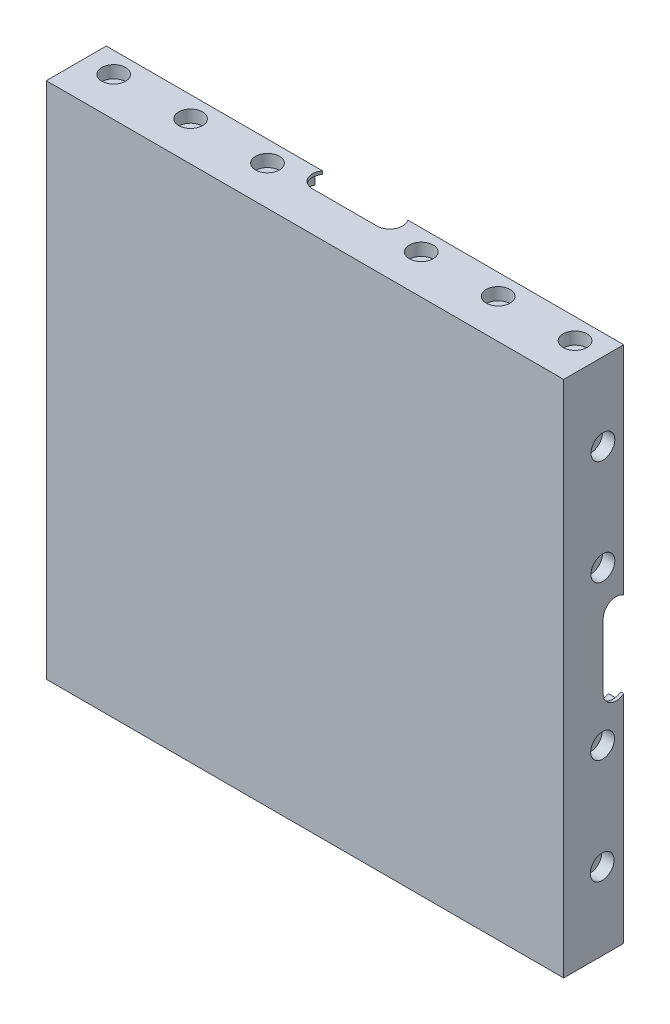
SolidWorks part; units mm, degrees
note: The reader was unsure of these and kept them because the rebuilt part matched: shared geometry of "Sketch1<3>", "Sketch1<4>", "Sketch9<3>", "Sketch9<4>", "Sketch13<2>", "Sketch14<2>".
ref_plane "Front Plane" through (0, 0, 0) normal (0, 0, 1) x (1, 0, 0)
ref_plane "Top Plane" through (0, 0, 0) normal (0, 1, 0) x (1, 0, 0)
ref_plane "Right Plane" through (0, 0, 0) normal (1, 0, 0) x (0, 0, -1)
sketch "Sketch1" plane through (0, 0, 0) normal (0, 0, 1) x (1, 0, 0)
  line L6 (-63, 3.7) -> (-61.15, 3.7) construction
  line L7 (-63, -63) -> (63, -63)
  line L8 (-63, -63) -> (-63, 63)
  line L9 (-63, 63) -> (63, 63)
  line L10 (63, -63) -> (63, 63)
  line L11 (-61, 61) -> (61, 61)
  line L12 (-61, 61) -> (-61, -61)
  line L13 (-61, -61) -> (61, -61)
  line L14 (61, 61) -> (61, -61)
  line L15 (-63, 7.7) -> (-61, 7.7)
  line L16 (-63, 7.7) -> (-63, -7.7)
  line L17 (-63, -7.7) -> (-61, -7.7)
  line L18 (-61, 7.7) -> (-61, -7.7)
  line L19 (-61.15, -3.7) -> (-63, -3.7) construction
  line L20 (-3.7, 61.45) -> (-3.7, 63) construction
  line L21 (-7.7, 61) -> (7.7, 61)
  line L22 (-7.7, 61) -> (-7.7, 63)
  line L23 (-7.7, 63) -> (7.7, 63)
  line L24 (7.7, 61) -> (7.7, 63)
  line L26 (3.7, 63) -> (3.7, 61.45) construction
  line L27 (-61, 0) -> (61, 0) construction
  line L28 (0, 61) -> (0, -61) construction
  line L29 (63, -7.7) -> (61, -7.7)
  line L30 (61, 7.7) -> (61, -7.7)
  line L31 (63, 7.7) -> (61, 7.7)
  line L32 (63, 7.7) -> (63, -7.7)
  line L33 (-7.7, -63) -> (7.7, -63)
  line L34 (7.7, -61) -> (7.7, -63)
  line L35 (-7.7, -61) -> (7.7, -61)
  line L36 (-7.7, -61) -> (-7.7, -63)
  dimension "D1" = 4
  dimension "D2" = 4
  dimension "D3" = 4
  dimension "D4" = 4
  dimension "D5" = 2
  dimension "D6" = 2
  dimension "D7" = 2
  dimension "D8" = 2
extrude "Boss-Extrude1" add sketch "Sketch1" along normal blind 3 from offset 0.4 contours L11 L22 L9 L8 L15 L12 | L36 L13 L12 L17 L8 L7 | L13 L34 L7 L10 L29 L14 | L31 L10 L9 L24 L11 L14
extrude "Boss-Extrude2" add sketch "Sketch1<3>" along normal up to surface (2.85 mm away) from surface at 3.4 contours L8 L17 L12 L15 | L11 L22 L9 L8 L15 L12 | L36 L13 L12 L17 L8 L7 | L13 L34 L7 L10 L29 L14 | L31 L10 L9 L24 L11 L14 | L10 L31 L14 L29 | L13 L36 L7 L34 | L11 L24 L9 L22 starting at face at (43.9, 43.9, 3.4)
sketch "Sketch1<3>" plane through (0, 0, 0) normal (0, 0, 1) x (1, 0, 0) same geometry as "Sketch1"
extrude "Boss-Extrude3" add sketch "Sketch1<4>" against normal up to surface (7.7671 mm away) from surface contours L14 L11 L12 L13 | L8 L17 L12 L15 | L11 L22 L9 L8 L15 L12 | L36 L13 L12 L17 L8 L7 | L13 L36 L7 L34 | L13 L34 L7 L10 L29 L14 | L10 L31 L14 L29 | L31 L10 L9 L24 L11 L14 | L11 L24 L9 L22
sketch "Sketch1<4>" plane through (0, 0, 0) normal (0, 0, 1) x (1, 0, 0) same geometry as "Sketch1"
sketch "Sketch2" plane through (0, 63, 0) normal (0, 1, 0) x (1, 0, 0)
  line L0 (-8.5, -0.4) -> (8.5, -0.4) construction
  line L1 (-8.5, 4.6) -> (8.5, 4.6)
  line L2 (-8.5, -5.4) -> (8.5, -5.4)
  line L3 (-8.5, 3.6) -> (8.5, 3.6) construction
  line L4 (8.5, -4.4) -> (-8.5, -4.4) construction
  line L6 (-63, 1.6) -> (63, 1.6)
  line L7 (-63, 1.6) -> (-63, -14.0171)
  line L8 (-63, -14.0171) -> (63, -14.0171)
  line L9 (63, 1.6) -> (63, -14.0171)
  arc A0 (-8.5, 4.6) -> (-8.5, -5.4) centre (-8.5, -0.4) ccw
  arc A1 (8.5, -5.4) -> (8.5, 4.6) centre (8.5, -0.4) ccw
  arc A2 (-8.5, 3.6) -> (-8.5, -4.4) centre (-8.5, -0.4) ccw construction
  point P2 (0, -0.4)
  point P7 (0, 0)
  point P8 (0, 0)
  point P9 (62.1074, -13.2373)
  point P20 (-12.5, -0.4)
  point P21 (-13.5, -0.4)
  point P23 (13.5, -0.4)
  dimension "D1" = 1
  dimension "D2" = 1
  dimension "D3" = 1
  dimension "D4" = 1
extrude "Boss-Extrude4" add sketch "Sketch2" along normal offset from surface (3.85 mm away) 0.2
sketch "Sketch3" plane through (63, 0, 0) normal (1, 0, 0) x (0, 0, -1)
  line L0 (-0.4, 8.5) -> (-0.4, -8.5) construction
  line L1 (4.6, 8.5) -> (4.6, -8.5)
  line L2 (-5.4, 8.5) -> (-5.4, -8.5)
  line L3 (3.6, 8.5) -> (3.6, -8.5) construction
  line L4 (-4.4, -8.5) -> (-4.4, 8.5) construction
  line L6 (1.6, 66.85) -> (-14.0171, 66.85)
  line L7 (1.6, 66.85) -> (1.6, -63)
  line L8 (1.6, -63) -> (-14.0171, -63)
  line L9 (-14.0171, 66.85) -> (-14.0171, -63)
  arc A0 (4.6, 8.5) -> (-5.4, 8.5) centre (-0.4, 8.5) ccw
  arc A1 (-5.4, -8.5) -> (4.6, -8.5) centre (-0.4, -8.5) ccw
  arc A2 (3.6, 8.5) -> (-4.4, 8.5) centre (-0.4, 8.5) ccw construction
  point P2 (-0.4, 0)
  point P12 (-0.4, -13.5)
  point P16 (-0.4, 12.5)
  point P17 (-0.4, 13.5)
  point P22 (0, 0)
  point P23 (0, 0)
  point P24 (0, 0)
  point P25 (-12.5051, -61.7984)
  dimension "D1" = 1
  dimension "D2" = 1
  dimension "D3" = 1
  dimension "D4" = 1
extrude "Boss-Extrude6" add sketch "Sketch3" along normal offset from surface (3.45 mm away) 0.2
sketch "Sketch4" plane through (0, -63, 0) normal (0, -1, 0) x (1, 0, 0)
  line L0 (8.5, 0.4) -> (-8.5, 0.4) construction
  line L1 (8.5, -4.6) -> (-8.5, -4.6)
  line L2 (8.5, 5.4) -> (-8.5, 5.4)
  line L3 (8.5, -3.6) -> (-8.5, -3.6) construction
  line L4 (-8.5, 4.4) -> (8.5, 4.4) construction
  line L6 (66.45, -1.6) -> (-63, -1.6)
  line L7 (66.45, -1.6) -> (66.45, 14.0171)
  line L8 (66.45, 14.0171) -> (-63, 14.0171)
  line L9 (-63, -1.6) -> (-63, 14.0171)
  arc A0 (8.5, -4.6) -> (8.5, 5.4) centre (8.5, 0.4) ccw
  arc A1 (-8.5, 5.4) -> (-8.5, -4.6) centre (-8.5, 0.4) ccw
  arc A2 (8.5, -3.6) -> (8.5, 4.4) centre (8.5, 0.4) ccw construction
  point P2 (0, 0.4)
  point P7 (0, 0)
  point P13 (-13.5, 0.4)
  point P14 (13.5, 0.4)
  point P18 (12.5, 0.4)
  point P23 (0, 0)
  point P26 (-61.9955, 13.332)
  dimension "D1" = 1
  dimension "D2" = 1
  dimension "D3" = 1
  dimension "D4" = 1
extrude "Boss-Extrude9" add sketch "Sketch4" along normal offset from surface (3.55 mm away) 0.2
sketch "Sketch5" plane through (-63, 0, 0) normal (-1, 0, 0) x (0, 0, 1)
  line L0 (0.4, -8.5) -> (0.4, 8.5) construction
  line L1 (-4.6, -8.5) -> (-4.6, 8.5)
  line L2 (5.4, -8.5) -> (5.4, 8.5)
  line L3 (-3.6, -8.5) -> (-3.6, 8.5) construction
  line L5 (4.4, 8.5) -> (4.4, -8.5) construction
  line L7 (-1.6, -66.55) -> (14.0171, -66.55)
  line L8 (-1.6, -66.55) -> (-1.6, 66.85)
  line L9 (-1.6, 66.85) -> (14.0171, 66.85)
  line L10 (14.0171, -66.55) -> (14.0171, 66.85)
  arc A0 (-4.6, -8.5) -> (5.4, -8.5) centre (0.4, -8.5) ccw
  arc A1 (5.4, 8.5) -> (-4.6, 8.5) centre (0.4, 8.5) ccw
  arc A3 (-3.6, -8.5) -> (4.4, -8.5) centre (0.4, -8.5) ccw construction
  point P2 (0.4, 0)
  point P12 (0.4, 13.5)
  point P14 (0.4, -12.5)
  point P15 (0.4, -13.5)
  point P24 (0, 0)
  point P25 (0, 0)
  point P26 (13.1514, 63.8467)
  point P29 (0, 0)
  dimension "D3" = 1
  dimension "D1" = 1
  dimension "D2" = 1
  dimension "D4" = 1
extrude "Boss-Extrude10" add sketch "Sketch5" along normal offset from surface (3.55 mm away) 0.2
sketch "Sketch6" plane through (-66.55, 0, 0) normal (-1, 0, 0) x (0, 0, 1)
  line L0 (0.4, -8.4) -> (0.4, 8.4) construction
  line L1 (-2.95, -8.4) -> (-2.95, 8.4)
  line L2 (3.75, -8.4) -> (3.75, 8.4)
  line L3 (-2.45, -8.4) -> (-2.45, 8.4) construction
  line L4 (3.25, 8.4) -> (3.25, -8.4) construction
  line L6 (-1.6, -66.55) -> (14.0171, -66.55)
  line L7 (-1.6, -66.55) -> (-1.6, 66.85)
  line L8 (-1.6, 66.85) -> (14.0171, 66.85)
  line L9 (14.0171, -66.55) -> (14.0171, 66.85)
  arc A0 (-2.95, -8.4) -> (3.75, -8.4) centre (0.4, -8.4) ccw
  arc A1 (3.75, 8.4) -> (-2.95, 8.4) centre (0.4, 8.4) ccw
  arc A2 (3.25, 8.4) -> (-2.45, 8.4) centre (0.4, 8.4) ccw construction
  point P2 (0.4, 0)
  point P14 (0.4, 11.25)
  point P15 (0.4, 11.75)
  point P17 (0.4, -11.75)
  point P24 (0, 0)
  point P26 (13.7412, 65.7953)
  dimension "D1" = 0.5
  dimension "D2" = 0.5
  dimension "D3" = 0.5
  dimension "D4" = 0.5
extrude "Boss-Extrude11" add sketch "Sketch6" along normal up to surface (0.8 mm away)
sketch "Sketch7" plane through (0, -66.55, 0) normal (0, -1, 0) x (1, 0, 0)
  line L0 (8.4, 0.4) -> (-8.4, 0.4) construction
  line L6 (8.4, -2.95) -> (-8.4, -2.95)
  line L7 (8.4, 3.75) -> (-8.4, 3.75)
  line L8 (8.4, -2.45) -> (-8.4, -2.45) construction
  line L9 (-8.4, 3.25) -> (8.4, 3.25) construction
  line L11 (66.45, -1.6) -> (-67.35, -1.6)
  line L12 (66.45, -1.6) -> (66.45, 14.0171)
  line L13 (66.45, 14.0171) -> (-67.35, 14.0171)
  line L14 (-67.35, -1.6) -> (-67.35, 14.0171)
  arc A2 (-8.4, 3.25) -> (-8.4, -2.45) centre (-8.4, 0.4) ccw construction
  arc A3 (8.4, -2.95) -> (8.4, 3.75) centre (8.4, 0.4) ccw
  arc A4 (-8.4, 3.75) -> (-8.4, -2.95) centre (-8.4, 0.4) ccw
  point P2 (0, 0)
  point P3 (0, 0.4)
  point P10 (11.75, 0.4)
  point P11 (0, 0)
  point P16 (-11.25, 0.4)
  point P19 (-11.75, 0.4)
  point P23 (-66.7645, 13.4104)
  dimension "D1" = 0.5
  dimension "D2" = 0.5
  dimension "D3" = 0.5
  dimension "D4" = 0.5
extrude "Boss-Extrude12" add sketch "Sketch7" along normal up to surface (0.8 mm away)
sketch "Sketch8" plane through (66.45, 0, 0) normal (1, 0, 0) x (0, 0, -1)
  line L0 (-0.4, 8.4) -> (-0.4, -8.4) construction
  line L1 (1.6, 66.85) -> (-14.0171, 66.85)
  line L2 (1.6, 66.85) -> (1.6, -67.35)
  line L3 (1.6, -67.35) -> (-14.0171, -67.35)
  line L4 (-14.0171, 66.85) -> (-14.0171, -67.35)
  line L5 (2.95, 8.4) -> (2.95, -8.4)
  line L6 (-3.75, 8.4) -> (-3.75, -8.4)
  line L7 (-3.25, -8.4) -> (-3.25, 8.4) construction
  line L8 (2.45, 8.4) -> (2.45, -8.4) construction
  arc A0 (2.95, 8.4) -> (-3.75, 8.4) centre (-0.4, 8.4) ccw
  arc A1 (-3.75, -8.4) -> (2.95, -8.4) centre (-0.4, -8.4) ccw
  arc A2 (-3.25, -8.4) -> (2.45, -8.4) centre (-0.4, -8.4) ccw construction
  point P8 (-0.4, 0)
  point P13 (-0.4, 11.75)
  point P18 (-0.4, -11.25)
  point P19 (-0.4, -11.75)
  point P22 (0, 0)
  point P23 (-13.3009, -66.3561)
  dimension "D1" = 0.5
  dimension "D2" = 0.5
  dimension "D3" = 0.5
  dimension "D4" = 0.5
extrude "Boss-Extrude13" add sketch "Sketch8" along normal up to surface (0.8 mm away)
sketch "Sketch9" plane through (0, 66.85, 0) normal (0, 1, 0) x (1, 0, 0)
  line L0 (-8.4, -0.4) -> (8.4, -0.4) construction
  line L1 (-8.4, 2.95) -> (8.4, 2.95)
  line L2 (-8.4, -3.75) -> (8.4, -3.75)
  line L3 (-8.4, 2.45) -> (8.4, 2.45) construction
  line L4 (8.4, -3.25) -> (-8.4, -3.25) construction
  line L6 (-67.35, 1.6) -> (67.25, 1.6)
  line L7 (-67.35, 1.6) -> (-67.35, -14.0171)
  line L8 (-67.35, -14.0171) -> (67.25, -14.0171)
  line L9 (67.25, 1.6) -> (67.25, -14.0171)
  arc A0 (-8.4, 2.95) -> (-8.4, -3.75) centre (-8.4, -0.4) ccw
  arc A1 (8.4, -3.75) -> (8.4, 2.95) centre (8.4, -0.4) ccw
  arc A2 (8.4, -3.25) -> (8.4, 2.45) centre (8.4, -0.4) ccw construction
  point P2 (0, -0.4)
  point P12 (-11.75, -0.4)
  point P16 (11.25, -0.4)
  point P17 (11.75, -0.4)
  point P24 (0, 0)
  point P25 (66.711, -13.2218)
  arc M3 (13.0826, 1.6) -> (8.5, -5.4) centre (8.5, -0.4) cw
  line M4 (8.5, -5.4) -> (-8.5, -5.4)
  arc M5 (-8.5, -5.4) -> (-13.0826, 1.6) centre (-8.5, -0.4) cw
  dimension "D1" = 0.5
  dimension "D2" = 0.5
  dimension "D3" = 0.5
  dimension "D4" = 0.5
extrude "Boss-Extrude14" add sketch "Sketch9" along normal up to surface (0.8 mm away)
sketch "Sketch11" plane through (0, 0, -1.6) normal (0, 0, -1) x (-1, 0, 0)
  line L0 (63, 63) -> (63, -63) construction
  line L1 (-63.3, 63.3) -> (63.3, 63.3)
  line L2 (-63.3, 63.3) -> (-63.3, -63.3)
  line L3 (-63.3, -63.3) -> (63.3, -63.3)
  line L4 (63.3, 63.3) -> (63.3, -63.3)
  line L5 (63, 63) -> (13.0826, 63) construction
  line L6 (-63, -63) -> (-63, 63) construction
  dimension "D1" = 0.3
  dimension "D2" = 0.3
  dimension "D3" = 0.3
  dimension "D4" = 0.3
extrude "Cut-Extrude1" cut sketch "Sketch11" against normal up to surface (2 mm away) up to face at (42.4875, 42.4875, 0.4)
sketch "Sketch12" plane through (0, 0, -1.6) normal (0, 0, -1) x (-1, 0, 0)
  line L0 (-67.25, 67.65) -> (-63.3, 63.3) construction
  line L3 (63.3, 63.3) -> (67.35, 67.65) construction
  line L4 (63.3, -63.3) -> (67.35, -67.35) construction
  line L5 (-63.3, -63.3) -> (-67.25, -67.35) construction
  circle A0 centre (-64.9134, 65.0768) radius 1.8
  circle A1 centre (-64.9757, -65.0181) radius 1.8
  circle A2 centre (64.9971, -64.9971) radius 1.8
  circle A3 centre (64.9354, 65.0565) radius 1.8
  dimension "D1" = 3.6
  dimension "D2" = 2.4
  dimension "D3" = 2.4
  dimension "D4" = 2.4
  dimension "D5" = 2.4
extrude "Cut-Extrude2" cut sketch "Sketch12" against normal blind 5
extrude "Boss-Extrude15" add sketch "Sketch9<3>" against normal blind 0.15 from surface at 0 contours A1 L2 A0 L6 M5 M4 M3 starting at face at (0, 66.85, 2.0043)
sketch "Sketch9<3>" plane through (0, 66.85, 0) normal (0, 1, 0) x (1, 0, 0) same geometry as "Sketch9"
extrude "Cut-Extrude3" cut sketch "Sketch9<4>" against normal blind 0.15 from surface at 0.8 contours L8 L9 L6 L7 starting at face at (-0.025, 67.65, 3.849)
sketch "Sketch9<4>" plane through (0, 66.85, 0) normal (0, 1, 0) x (1, 0, 0) same geometry as "Sketch9"
sketch "Sketch13" plane through (-67.35, 0, 0) normal (-1, 0, 0) x (0, 0, 1)
  circle A0 centre (3.9003, -19.9937) radius 3.1
  circle A1 centre (3.9003, -19.9937) radius 3.1 construction
  circle A2 centre (4.0109, -47.2841) radius 3.1
  circle A3 centre (4.0109, -47.2841) radius 3.1 construction
  circle A4 centre (3.8192, 20.0094) radius 3.1
  circle A5 centre (3.8192, 20.0094) radius 3.1 construction
  circle A6 centre (3.8192, 47.3) radius 3.1
  circle A7 centre (3.8192, 47.3) radius 3.1 construction
extrude "Cut-Extrude4" cut sketch "Sketch13" against normal blind 3.2
extrude "Cut-Extrude5" cut sketch "Sketch13<2>" along normal blind 3.2 from surface at -134.6 starting at face at (67.25, 0.0375, 3.849)
sketch "Sketch13<2>" plane through (-67.35, 0, 0) normal (-1, 0, 0) x (0, 0, 1) same geometry as "Sketch13"
sketch "Sketch14" plane through (0, -67.35, 0) normal (0, -1, 0) x (1, 0, 0)
  line L0 (-127.35, 3.8192) -> (67.25, 3.8192) construction
  line L1 (67.25, -1.6) -> (67.25, 14.0171) construction
  line L2 (-8.4, 3.25) -> (8.4, 3.25) construction
  line L3 (0, 3.25) -> (0, 14.0171) construction
  line L5 (-67.35, 14.0171) -> (67.25, 14.0171) construction
  circle A0 centre (-20, 3.8192) radius 3.1
  circle A1 centre (-60, 3.8192) radius 3.1
  circle A2 centre (60, 3.8192) radius 3.1
  circle A3 centre (-40, 3.8192) radius 3.1
  circle A4 centre (40, 3.8192) radius 3.1
  circle A5 centre (20, 3.8192) radius 3.1
  point P13 (0, 3.25)
  point P24 (0, 0)
  point P25 (0, 0)
  point P26 (0, 0)
  dimension "D4" = 6.2
  dimension "D1" = 20
  dimension "D3" = 20
  dimension "D2" = 3
extrude "Cut-Extrude6" cut sketch "Sketch14" against normal blind 3.2
extrude "Cut-Extrude7" cut sketch "Sketch14<2>" along normal blind 3.2 from surface at -134.85 starting at face at (-0.025, 67.5, 3.849)
sketch "Sketch14<2>" plane through (0, -67.35, 0) normal (0, -1, 0) x (1, 0, 0) same geometry as "Sketch14"
sketch "Sketch15" plane through (0, 0, 6.25) normal (0, 0, -1) x (-1, 0, 0)
  circle A0 centre (-52.2, 58.5) radius 1.8
  circle A1 centre (-28.8, 58.5) radius 1.8
  circle A2 centre (-28.8, 34.7) radius 1.8
  circle A3 centre (-52.2, 34.7) radius 1.8
  circle A5 centre (-52.2, 58.5) radius 2.5 construction
  circle A6 centre (-52.2, 34.7) radius 2.5 construction
  circle A7 centre (-28.8, 34.7) radius 1.25 construction
  circle A8 centre (-28.8, 58.5) radius 2.5 construction
  circle A9 centre (-14.2, 58.5) radius 1.8
  circle A10 centre (9.2, 58.5) radius 1.8
  circle A11 centre (-14.2, 34.7) radius 1.8
  circle A12 centre (9.2, 34.7) radius 1.8
  circle A13 centre (-14.2, 58.5) radius 2.5 construction
  circle A14 centre (9.2, 58.5) radius 2.5 construction
  circle A15 centre (-14.2, 34.7) radius 1.25 construction
  circle A16 centre (9.2, 34.7) radius 2.5 construction
  circle A17 centre (-52.2, 58.5) radius 2.6
  circle A18 centre (-52.2, 34.7) radius 2.6
  circle A19 centre (-28.8, 34.7) radius 2.6
  circle A20 centre (-14.2, 34.7) radius 2.6
  circle A21 centre (9.2, 34.7) radius 2.6
  circle A22 centre (9.2, 58.5) radius 2.6
  circle A23 centre (-14.2, 58.5) radius 2.6
  circle A24 centre (-28.8, 58.5) radius 2.6
  dimension "D1" = 3.6
  dimension "D2" = 5.2
extrude "Boss-Extrude17" add sketch "Sketch15" along normal up to surface (5.85 mm away) up to face at (41.7, 41.7, 0.4)
fillet "Fillet1" radius 4.5 8 edges at (-9.2, 37.3, 6.25) (-9.2, 55.9, 6.25) (14.2, 55.9, 6.25) (14.2, 37.3, 6.25) (28.8, 37.3, 6.25) (52.2, 37.3, 6.25) (28.8, 55.9, 6.25) (52.2, 55.9, 6.25)
